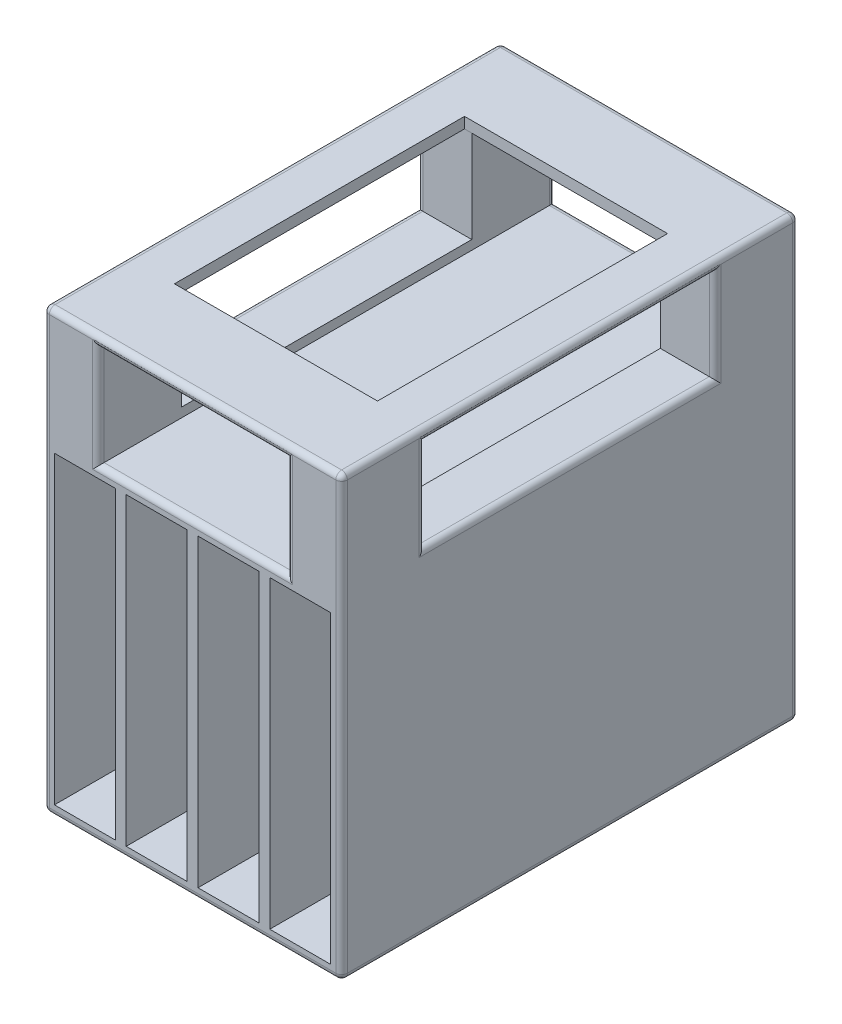
SolidWorks part; units mm, degrees
ref_plane "Front Plane" through (0, 0, 0) normal (0, 0, 1) x (1, 0, 0)
ref_plane "Top Plane" through (0, 0, 0) normal (0, 1, 0) x (1, 0, 0)
ref_plane "Right Plane" through (0, 0, 0) normal (1, 0, 0) x (0, 0, -1)
sketch "Sketch7" plane through (0, 0, 0) normal (0, 0, 1) x (1, 0, 0)
  line L1 (43.1135, -134.4375) -> (-59.6365, -134.4375)
  line L2 (43.1135, -134.4375) -> (43.1135, 16.8125)
  line L3 (43.1135, 16.8125) -> (-59.6365, 16.8125)
  line L4 (-59.6365, -134.4375) -> (-59.6365, 16.8125)
  dimension "D1" = 102.75
  dimension "D2" = 151.25
extrude "Boss-Extrude4" add sketch "Sketch7" along normal blind 157.5
sketch "Sketch9" plane through (0, 0, 157.5) normal (0, 0, 1) x (1, 0, 0)
  line L0 (43.1135, 16.8125) -> (-59.6365, 16.8125) construction
  line L1 (-40.7615, 13.0625) -> (24.2385, 13.0625)
  line L2 (-40.7615, 13.0625) -> (-40.7615, -21.9375)
  line L3 (-40.7615, -21.9375) -> (24.2385, -21.9375)
  line L4 (24.2385, 13.0625) -> (24.2385, -21.9375)
  line L5 (-59.6365, -134.4375) -> (43.1135, -134.4375) construction
  line L6 (-55.8865, -130.6875) -> (-34.8865, -130.6875)
  line L7 (-55.8865, -130.6875) -> (-55.8865, -25.6875)
  line L8 (-55.8865, -25.6875) -> (-34.8865, -25.6875)
  line L9 (-34.8865, -130.6875) -> (-34.8865, -25.6875)
  line L10 (-59.6365, 16.8125) -> (-59.6365, -134.4375) construction
  line L11 (43.1135, -134.4375) -> (43.1135, 16.8125) construction
  line L12 (-31.1365, -130.6875) -> (-10.1365, -130.6875)
  line L13 (-31.1365, -130.6875) -> (-31.1365, -25.6875)
  line L14 (-31.1365, -25.6875) -> (-10.1365, -25.6875)
  line L15 (-10.1365, -130.6875) -> (-10.1365, -25.6875)
  line L16 (-6.3865, -130.6875) -> (14.6135, -130.6875)
  line L17 (-6.3865, -130.6875) -> (-6.3865, -25.6875)
  line L18 (-6.3865, -25.6875) -> (14.6135, -25.6875)
  line L19 (14.6135, -130.6875) -> (14.6135, -25.6875)
  line L20 (18.3635, -130.6875) -> (39.3635, -130.6875)
  line L21 (18.3635, -130.6875) -> (18.3635, -25.6875)
  line L22 (18.3635, -25.6875) -> (39.3635, -25.6875)
  line L23 (39.3635, -130.6875) -> (39.3635, -25.6875)
  dimension "D1" = 3.75
  dimension "D2" = 35
  dimension "D3" = 65
  dimension "D4" = 18.875
  dimension "D5" = 105
  dimension "D6" = 3.75
  dimension "D7" = 21
  dimension "D8" = 3.75
  dimension "D9" = 3.75
  dimension "D10" = 21
  dimension "D11" = 3.75
  dimension "D12" = 21
  dimension "D13" = 21
  dimension "D14" = 3.75
extrude "Cut-Extrude5" cut sketch "Sketch9" against normal blind 157.5
sketch "Sketch10" plane through (-59.6365, 0, 0) normal (-1, 0, 0) x (0, 0, 1)
  line L0 (157.5, 16.8125) -> (0, 16.8125) construction
  line L1 (28.75, 13.0625) -> (128.75, 13.0625)
  line L2 (28.75, 13.0625) -> (28.75, -18.714)
  line L3 (28.75, -18.714) -> (128.75, -18.714)
  line L4 (128.75, 13.0625) -> (128.75, -18.714)
  line L5 (0, 16.8125) -> (0, -134.4375) construction
  dimension "D1" = 3.75
  dimension "D2" = 28.75
  dimension "D3" = 100
extrude "Cut-Extrude6" cut sketch "Sketch10" against normal blind 157.5
fillet "Fillet3" radius 2 1 edges at (43.1135, 16.8125, 78.75)
fillet "Fillet4" radius 2 7 edges at (43.1135, -59.8125, 0) (42.5277, 16.2267, 0) (43.1135, -59.8125, 157.5) (42.5277, 16.2267, 157.5) (-59.6365, 16.8125, 78.75) (-9.2615, 16.8125, 0) (-9.2615, 16.8125, 157.5)
fillet "Fillet6" radius 2 5 edges at (-59.0507, 16.2267, 0.5858) (-59.0507, 16.2267, 156.9142) (-59.6365, -134.4375, 78.75) (-59.6365, -59.8125, 0) (-59.6365, -59.8125, 157.5)
fillet "Fillet7" radius 2 7 edges at (-59.0507, -133.8518, 156.9142) (-59.0507, -133.8518, 0.5858) (42.5277, -134.4375, 156.9142) (43.1135, -134.4375, 78.75) (42.5277, -134.4375, 0.5858) (-8.2615, -134.4375, 0) (-8.2615, -134.4375, 157.5)
fillet "Fillet8" radius 2 4 edges at (24.2385, -4.4375, 0) (-8.2615, 13.0625, 0) (-40.7615, -4.4375, 0) (-8.2615, -21.9375, 0)
fillet "Fillet9" radius 2 12 edges at (-59.6365, 13.0625, 78.75) (-59.6365, -2.8258, 28.75) (-59.6365, -18.714, 78.75) (-59.6365, -2.8258, 128.75) (43.1135, -2.8258, 28.75) (43.1135, 13.0625, 78.75) (43.1135, -2.8258, 128.75) (43.1135, -18.714, 78.75) (24.2385, -4.4375, 157.5) (-8.2615, 13.0625, 157.5) (-8.2615, -21.9375, 157.5) (-40.7615, -4.4375, 157.5)
sketch "Sketch13" plane through (0, 16.8125, 0) normal (0, 1, 0) x (1, 0, 0)
  line L0 (-42.6365, -157.4961) -> (26.1135, -157.4961) construction
  line L1 (26.7346, -128.7461) -> (-43.2654, -128.7461)
  line L2 (26.7346, -128.7461) -> (26.7346, -28.7461)
  line L3 (26.7346, -28.7461) -> (-43.2654, -28.7461)
  line L4 (-43.2654, -128.7461) -> (-43.2654, -28.7461)
  line L5 (43.1096, -130.625) -> (43.1096, -26.875) construction
  dimension "D1" = 100
  dimension "D2" = 70
  dimension "D3" = 28.75
  dimension "D4" = 16.375
extrude "Cut-Extrude7" cut sketch "Sketch13" against normal blind 3.75
